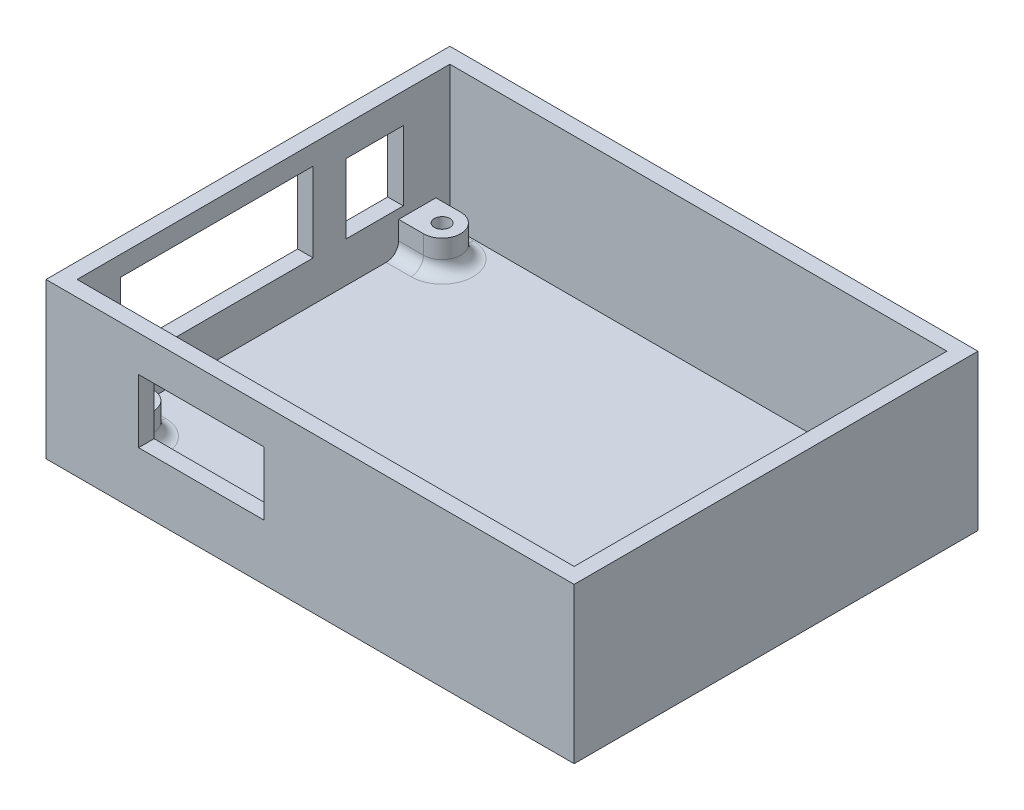
SolidWorks part; units mm, degrees
ref_plane "前视基准面" through (0, 0, 0) normal (0, 0, 1) x (1, 0, 0)
ref_plane "上视基准面" through (0, 0, 0) normal (0, 1, 0) x (1, 0, 0)
ref_plane "右视基准面" through (0, 0, 0) normal (1, 0, 0) x (0, 0, -1)
sketch "草图1" plane through (0, 0, 0) normal (0, 1, 0) x (1, 0, 0)
  line L1 (-42.5, -32.5) -> (42.5, -32.5)
  line L2 (-42.5, -32.5) -> (-42.5, 32.5)
  line L3 (-42.5, 32.5) -> (42.5, 32.5)
  line L4 (42.5, -32.5) -> (42.5, 32.5)
  line L5 (-42.5, -32.5) -> (42.5, 32.5) construction
  line L6 (-42.5, 32.5) -> (42.5, -32.5) construction
  point P0 (0, 0)
  dimension "D1" = 65
  dimension "D2" = 85
extrude "凸台-拉伸1" add sketch "草图1" along normal blind 25
shell "抽壳1" thickness 2.5 removed face at (0, 25, 0)
sketch "草图2" plane through (0, 2.5, 0) normal (0, 1, 0) x (1, 0, 0)
  line L0 (-36, 0) -> (32, 0) construction
  line L1 (32, 24.75) -> (-36, 24.75) construction
  line L2 (32, 24.75) -> (32, -24.75) construction
  line L3 (32, -24.75) -> (-36, -24.75) construction
  line L4 (-36, 24.75) -> (-36, -24.75) construction
  line L5 (-40, 30) -> (-40, -30) construction
  line L6 (-36, 27.75) -> (-40, 27.75)
  line L7 (-36, 21.75) -> (-40, 21.75)
  line L8 (-40, 27.75) -> (-40, 21.75)
  line L9 (-36, -21.75) -> (-40, -21.75)
  line L10 (-40, -21.75) -> (-40, -27.75)
  line L11 (-40, 30) -> (-40, -30) construction
  line L12 (-40, -27.75) -> (-36, -27.75)
  arc A0 (-36, 21.75) -> (-36, 27.75) centre (-36, 24.75) ccw
  circle A1 centre (32, 24.75) radius 3
  circle A2 centre (32, -24.75) radius 3
  arc A3 (-36, -27.75) -> (-36, -21.75) centre (-36, -24.75) ccw
  circle A4 centre (32, 24.75) radius 1.25
  circle A5 centre (32, -24.75) radius 1.25
  circle A6 centre (-36, -24.75) radius 1.25
  circle A7 centre (-36, 24.75) radius 1.25
  dimension "D4" = 6
  dimension "D5" = 2.5
  dimension "D1" = 49.5
  dimension "D2" = 68
  dimension "D3" = 4
extrude "凸台-拉伸2" add sketch "草图2" along normal blind 5
sketch "草图3" plane through (0, 0, 30) normal (0, 0, -1) x (-1, 0, 0)
  line L1 (27.6, 19.2) -> (7.4, 19.2)
  line L2 (27.6, 19.2) -> (27.6, 9)
  line L3 (27.6, 9) -> (7.4, 9)
  line L4 (7.4, 19.2) -> (7.4, 9)
  line L6 (27.6, 19.2) -> (7.4, 9) construction
  line L7 (7.4, 19.2) -> (27.6, 9) construction
  line L8 (40, 25) -> (40, 2.5) construction
  line L9 (40, 2.5) -> (-40, 2.5) construction
  point P4 (17.5, 14.1)
  dimension "D1" = 20.2
  dimension "D2" = 10.2
  dimension "D3" = 22.5
  dimension "D4" = 11.6
extrude "切除-拉伸1" cut sketch "草图3" against normal through all
sketch "草图4" plane through (-40, 0, 0) normal (1, 0, 0) x (0, 0, -1)
  line L1 (22.5, 20.2) -> (13.3, 20.2)
  line L2 (22.5, 20.2) -> (22.5, 9)
  line L3 (22.5, 9) -> (13.3, 9)
  line L4 (13.3, 20.2) -> (13.3, 9)
  line L5 (8, 21.8) -> (-23, 21.8)
  line L6 (8, 21.8) -> (8, 9)
  line L7 (8, 9) -> (-23, 9)
  line L8 (-23, 21.8) -> (-23, 9)
  line L11 (8, 21.8) -> (-23, 9) construction
  line L12 (-23, 21.8) -> (8, 9) construction
  line L13 (13.3, 20.2) -> (22.5, 9) construction
  line L14 (22.5, 20.2) -> (13.3, 9) construction
  line L15 (21.75, 2.5) -> (-21.75, 2.5) construction
  line L16 (30, 25) -> (30, 2.5) construction
  line L17 (-30, 25) -> (-30, 2.5) construction
  point P10 (-7.5, 15.4)
  point P12 (17.9, 14.6)
  dimension "D1" = 9.2
  dimension "D2" = 11.2
  dimension "D3" = 12.8
  dimension "D4" = 31
  dimension "D5" = 12.1
  dimension "D6" = 22.5
  dimension "D7" = 12.1
extrude "切除-拉伸2" cut sketch "草图4" against normal through all
fillet "圆角1" radius 2 8 edges at (32, 2.5, -27.75) (32, 2.5, 21.75) (-38, 2.5, -21.75) (-38, 2.5, -27.75) (-38, 2.5, 27.75) (-38, 2.5, 21.75) (-33, 2.5, -24.75) (-33, 2.5, 24.75)
